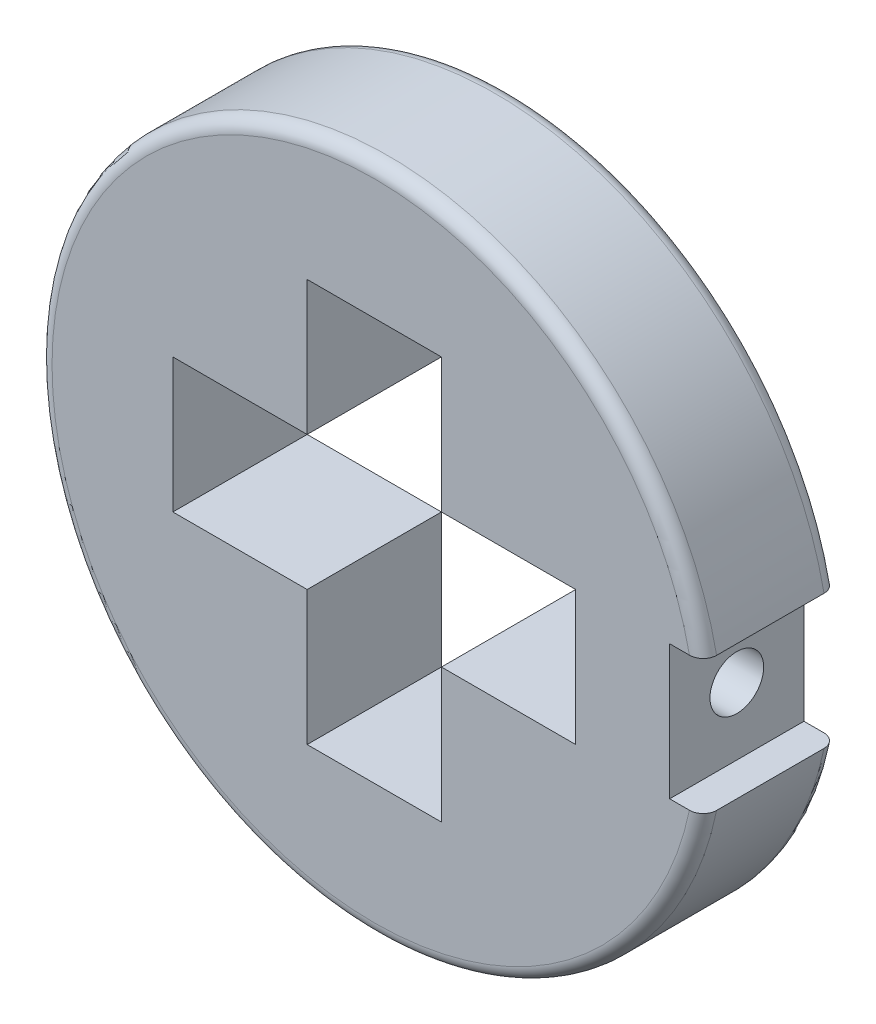
SolidWorks part; units mm, degrees
ref_plane "Front Plane" through (0, 0, 0) normal (0, 0, 1) x (1, 0, 0)
ref_plane "Top Plane" through (0, 0, 0) normal (0, 1, 0) x (1, 0, 0)
ref_plane "Right Plane" through (0, 0, 0) normal (1, 0, 0) x (0, 0, -1)
sketch "Sketch1" plane through (0, 0, 0) normal (0, 0, 1) x (1, 0, 0)
  circle A0 centre (0, 0) radius 25
  dimension "D1" = 50
extrude "Boss-Extrude1" add sketch "Sketch1" along normal blind 10
sketch "Sketch2" plane through (0, 0, 10) normal (0, 0, 1) x (1, 0, 0)
  line L0 (5, -5) -> (15, -5)
  line L1 (-5, -15) -> (5, -15)
  line L2 (-5, -15) -> (-5, -5)
  line L3 (-5, 15) -> (5, 15)
  line L4 (5, -15) -> (5, -5)
  line L5 (-5, -15) -> (5, 15) construction
  line L6 (-5, 15) -> (5, -15) construction
  line L7 (-15, 5) -> (-5, 5)
  line L8 (-15, 5) -> (-15, -5)
  line L9 (-15, -5) -> (-5, -5)
  line L10 (15, 5) -> (15, -5)
  line L11 (-15, 5) -> (15, -5) construction
  line L12 (-15, -5) -> (15, 5) construction
  line L13 (-5, 5) -> (-5, 15)
  line L14 (5, 5) -> (15, 5)
  line L15 (5, 5) -> (5, 15)
  point P0 (0, 0)
  point P5 (0, 0)
  dimension "D1" = 10
  dimension "D2" = 10
  dimension "D3" = 10
  dimension "D4" = 10
extrude "Cut-Extrude1" cut sketch "Sketch2" against normal through all both and the other way through all
sketch "Sketch4" plane through (15, 0, 0) normal (-1, 0, 0) x (0, 0, 1)
  line L0 (0, 5) -> (10, -5) construction
  line L1 (10, -5) -> (10, 5) construction
  line L2 (10, 5) -> (0, -5) construction
  line L4 (4.7591, -4.2656) -> (8.5737, -2.3414)
  line L5 (8.5737, -2.3414) -> (8.8146, 1.9242)
  line L6 (8.8146, 1.9242) -> (5.2409, 4.2656)
  line L7 (5.2409, 4.2656) -> (1.4263, 2.3414)
  line L8 (1.4263, 2.3414) -> (1.1854, -1.9242)
  line L9 (1.1854, -1.9242) -> (4.7591, -4.2656)
  circle A0 centre (5, 0) radius 3.7 construction
extrude "Cut-Extrude2" cut sketch "Sketch4" against normal blind 3
sketch "Sketch5" plane through (18, 0, 0) normal (-1, 0, 0) x (0, 0, 1)
  line L0 (5.2409, 4.2656) -> (4.7591, -4.2656) construction
  circle A0 centre (5, 0) radius 2
  dimension "D1" = 4
extrude "Cut-Extrude4" cut sketch "Sketch5" against normal blind 13 contours A0
fillet "Fillet1" radius 1 2 edges at (25, 0, 0) (25, 0, 10)
sketch3d "3DSketch1"
  spline S0 degree 3 poles (25, -0.2644, 7) (25, 0.1322, 7) (24.999, 0.2622, 6.987) (24.995, 0.5178, 6.9362) (24.992, 0.6449, 6.8977) (24.9846, 0.8871, 6.7973) (24.9802, 1.0019, 6.7359) (24.9705, 1.2193, 6.5907) (24.9652, 1.3221, 6.5063) (24.9495, 1.5988, 6.2296) (24.939, 1.7478, 6.0066) (24.9242, 1.9473, 5.5253) (24.9199, 1.9999, 5.2621) (24.9199, 2.0001, 4.8706) (24.9209, 1.9871, 4.738) (24.9249, 1.936, 4.4815) (24.9279, 1.8983, 4.3568) (24.9353, 1.7981, 4.1146) (24.9398, 1.7355, 3.9975) (24.9494, 1.5908, 3.7809) (24.9546, 1.5082, 3.6798) (24.9652, 1.3216, 3.493) (24.9704, 1.2205, 3.4102) (24.9801, 1.004, 3.2654) (24.9845, 0.8871, 3.2027) (24.992, 0.6449, 3.1023) (24.9949, 0.5202, 3.0644) (24.9989, 0.2639, 3.0132) (25, 0.1313, 3) (25, -0.2604, 2.9999) (24.9957, -0.5236, 3.0522) (24.9809, -1.0051, 3.2514) (24.9705, -1.2283, 3.4002) (24.9548, -1.5051, 3.6765) (24.9495, -1.5896, 3.7793) (24.9398, -1.735, 3.9966) (24.9354, -1.7965, 4.1114) (24.928, -1.8971, 4.3533) (24.925, -1.9357, 4.4804) (24.9209, -1.9868, 4.7361) (24.9199, -1.9999, 4.866) (24.9199, -2.0001, 5.1301) (24.9209, -1.9873, 5.2604) (24.9249, -1.9367, 5.5161) (24.9279, -1.8983, 5.643) (24.9353, -1.7981, 5.8855) (24.9397, -1.7367, 6.0004) (24.9494, -1.5919, 6.2178) (24.9547, -1.5075, 6.3208) (24.9704, -1.231, 6.5977) (24.9808, -1.0081, 6.7469) (24.9956, -0.527, 6.9468) (25, -0.2644, 7) (25, 0.1322, 7) (24.999, 0.2622, 6.987) knots -0.0625 -0.0625 0 0 0.03125 0.03125 0.0625 0.0625 0.09375 0.09375 0.125 0.125 0.1875 0.1875 0.25 0.25 0.28125 0.28125 0.3125 0.3125 0.34375 0.34375 0.375 0.375 0.40625 0.40625 0.4375 0.4375 0.46875 0.46875 0.5 0.5 0.5625 0.5625 0.625 0.625 0.65625 0.65625 0.6875 0.6875 0.71875 0.71875 0.75 0.75 0.78125 0.78125 0.8125 0.8125 0.84375 0.84375 0.875 0.875 0.9375 0.9375 1 1 1.03125 1.03125 1.0625 only from (25, 0, 7) to (25, 0, 7) construction
  point P0 (24.927, 1.9093, 5.5951)
sketch3d "3DSketch2"
  spline S0 degree 3 poles (25, -0.2644, 7) (25, 0.1322, 7) (24.999, 0.2622, 6.987) (24.995, 0.5178, 6.9362) (24.992, 0.6449, 6.8977) (24.9846, 0.8871, 6.7973) (24.9802, 1.0019, 6.7359) (24.9705, 1.2193, 6.5907) (24.9652, 1.3221, 6.5063) (24.9495, 1.5988, 6.2296) (24.939, 1.7478, 6.0066) (24.9242, 1.9473, 5.5253) (24.9199, 1.9999, 5.2621) (24.9199, 2.0001, 4.8706) (24.9209, 1.9871, 4.738) (24.9249, 1.936, 4.4815) (24.9279, 1.8983, 4.3568) (24.9353, 1.7981, 4.1146) (24.9398, 1.7355, 3.9975) (24.9494, 1.5908, 3.7809) (24.9546, 1.5082, 3.6798) (24.9652, 1.3216, 3.493) (24.9704, 1.2205, 3.4102) (24.9801, 1.004, 3.2654) (24.9845, 0.8871, 3.2027) (24.992, 0.6449, 3.1023) (24.9949, 0.5202, 3.0644) (24.9989, 0.2639, 3.0132) (25, 0.1313, 3) (25, -0.2604, 2.9999) (24.9957, -0.5236, 3.0522) (24.9809, -1.0051, 3.2514) (24.9705, -1.2283, 3.4002) (24.9548, -1.5051, 3.6765) (24.9495, -1.5896, 3.7793) (24.9398, -1.735, 3.9966) (24.9354, -1.7965, 4.1114) (24.928, -1.8971, 4.3533) (24.925, -1.9357, 4.4804) (24.9209, -1.9868, 4.7361) (24.9199, -1.9999, 4.866) (24.9199, -2.0001, 5.1301) (24.9209, -1.9873, 5.2604) (24.9249, -1.9367, 5.5161) (24.9279, -1.8983, 5.643) (24.9353, -1.7981, 5.8855) (24.9397, -1.7367, 6.0004) (24.9494, -1.5919, 6.2178) (24.9547, -1.5075, 6.3208) (24.9704, -1.231, 6.5977) (24.9808, -1.0081, 6.7469) (24.9956, -0.527, 6.9468) (25, -0.2644, 7) (25, 0.1322, 7) (24.999, 0.2622, 6.987) knots -0.0625 -0.0625 0 0 0.03125 0.03125 0.0625 0.0625 0.09375 0.09375 0.125 0.125 0.1875 0.1875 0.25 0.25 0.28125 0.28125 0.3125 0.3125 0.34375 0.34375 0.375 0.375 0.40625 0.40625 0.4375 0.4375 0.46875 0.46875 0.5 0.5 0.5625 0.5625 0.625 0.625 0.65625 0.65625 0.6875 0.6875 0.71875 0.71875 0.75 0.75 0.78125 0.78125 0.8125 0.8125 0.84375 0.84375 0.875 0.875 0.9375 0.9375 1 1 1.03125 1.03125 1.0625 only from (25, 0, 7) to (25, 0, 7) construction
  point P0 (24.9992, 0.2052, 3.0106)
ref_plane "Plane2" through (24.9992, 0, 0) normal (1, 0, 0) x (0, 1, 0)
sketch "Sketch6" plane through (24.9992, 0, 0) normal (1, 0, 0) x (0, 1, 0)
  line L0 (0, 5) -> (0, -3.3415) construction
  line L2 (-5, 10) -> (5, 10)
  line L3 (-5, 10) -> (-5, 0)
  line L4 (-5, 0) -> (5, 0)
  line L5 (5, 10) -> (5, 0)
  line L6 (-5, 10) -> (5, 0) construction
  line L7 (-5, 0) -> (5, 10) construction
  dimension "D1" = 10
  dimension "D2" = 10
extrude "Cut-Extrude6" cut sketch "Sketch6" against normal blind 3 and the other way blind 3
